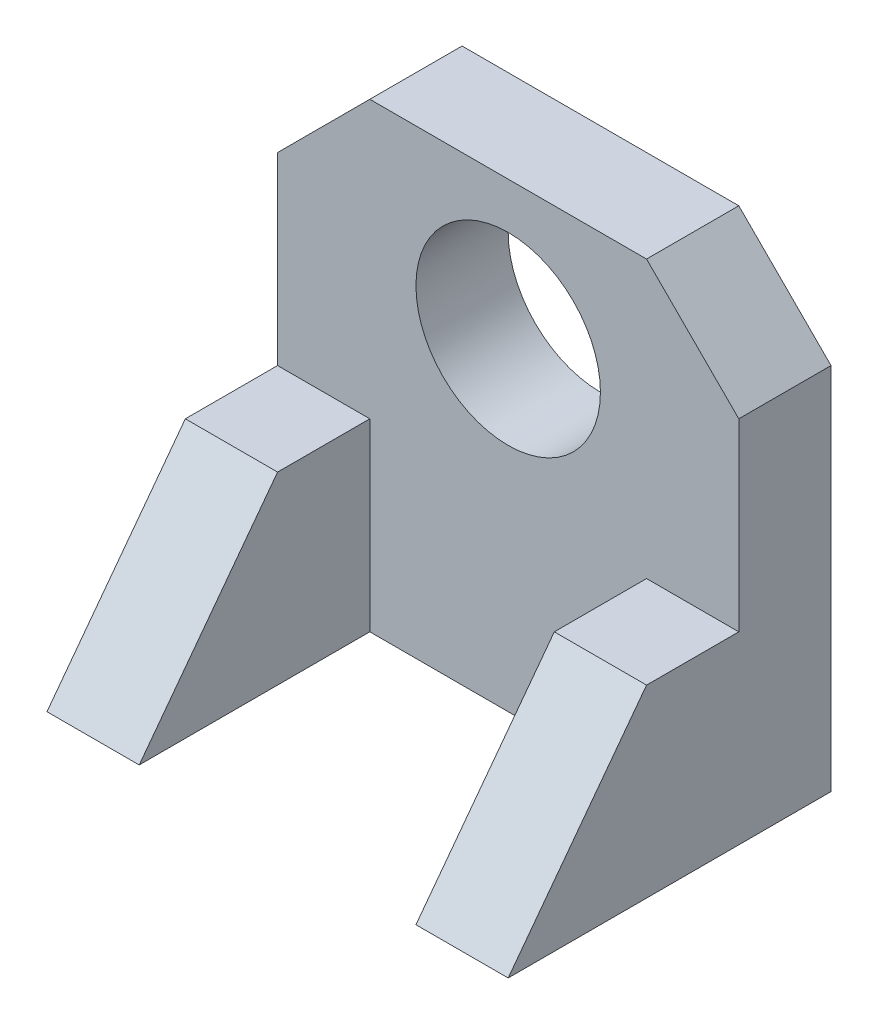
SolidWorks part; units mm, degrees
ref_plane "Front Plane" through (0, 0, 0) normal (0, 0, 1) x (1, 0, 0)
ref_plane "Top Plane" through (0, 0, 0) normal (0, 1, 0) x (1, 0, 0)
ref_plane "Right Plane" through (0, 0, 0) normal (1, 0, 0) x (0, 0, -1)
sketch "Sketch1" plane through (0, 0, 0) normal (0, 0, 1) x (1, 0, 0)
  line L0 (-25, 0) -> (25, 0)
  line L1 (-25, 0) -> (-25, 40)
  line L2 (-25, 40) -> (-15, 50)
  line L3 (-15, 50) -> (15, 50)
  line L4 (15, 50) -> (25, 40)
  line L5 (25, 40) -> (25, 0)
  line L6 (0, 50) -> (0, 35) construction
  circle A0 centre (0, 35) radius 10
  point P4 (0, 0)
  dimension "D1" = 50
  dimension "D2" = 40
  dimension "D3" = 10
  dimension "D4" = 10
  dimension "D5" = 10
  dimension "D6" = 10
extrude "Boss-Extrude1" add sketch "Sketch1" along normal blind 10
sketch "Sketch2" plane through (0, 0, 0) normal (1, 0, 0) x (0, 0, -1)
  line L0 (-10, 0) -> (-35, 0)
  line L1 (-35, 0) -> (-20, 20)
  line L2 (-20, 20) -> (-10, 20)
  line L3 (-10, 0) -> (-10, 40) construction
  line L8 (0, 0) -> (0, 40)
  line L9 (0, 40) -> (-10, 40)
  line L10 (-10, 40) -> (-10, 0)
  line L11 (-10, 0) -> (0, 0)
  line L12 (0, 0) -> (0, 40)
  line L13 (0, 40) -> (-10, 40)
  line L14 (-10, 40) -> (-10, 20)
  line L15 (-10, 0) -> (0, 0)
  dimension "D1" = 25
  dimension "D2" = 10
  dimension "D3" = 20
  dimension "D4" = 0
extrude "Boss-Extrude2" add sketch "Sketch2" along normal blind 10 from offset 15
extrude "Boss-Extrude3" add sketch "Sketch2<2>" against normal blind 10 from offset 15 offset against normal yes
sketch "Sketch2<2>" plane through (0, 0, 0) normal (1, 0, 0) x (0, 0, -1) same geometry as "Sketch2"
